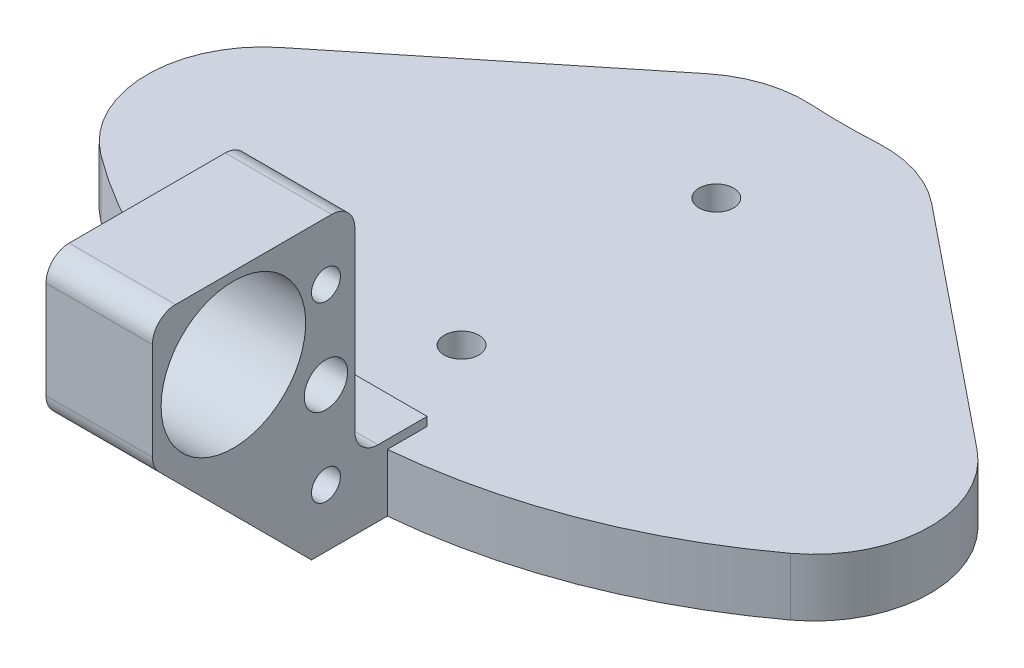
SolidWorks part; units mm, degrees
ref_plane "Front Plane" through (0, 0, 0) normal (0, 0, 1) x (1, 0, 0)
ref_plane "Top Plane" through (0, 0, 0) normal (0, 1, 0) x (1, 0, 0)
ref_plane "Right Plane" through (0, 0, 0) normal (1, 0, 0) x (0, 0, -1)
sketch "Sketch1" plane through (0, 0, 0) normal (0, 1, 0) x (1, 0, 0)
  line L0 (-49.3981, -39.9009) -> (-8.3458, -6.7413)
  line L1 (0, 0) -> (0, -63.5) construction
  line L2 (49.3981, -39.9009) -> (8.3458, -6.7413)
  arc A1 (-49.3981, -39.9009) -> (49.3981, -39.9009) centre (0, 0) ccw
  arc A2 (-8.3458, -6.7413) -> (8.3458, -6.7413) centre (0, 56.2079) ccw
  arc A3 (-56.9422, 28.1039) -> (-49.3981, -39.9009) centre (0, 0) ccw construction
  arc A4 (-56.9422, 28.1039) -> (-8.3458, -6.7413) centre (0, 56.2079) ccw construction
  arc A5 (8.3458, -6.7413) -> (56.9422, 28.1039) centre (0, 56.2079) ccw construction
  arc A6 (56.9422, 28.1039) -> (-56.9422, 28.1039) centre (0, 56.2079) ccw construction
  arc A7 (49.3981, -39.9009) -> (56.9422, 28.1039) centre (0, 0) ccw construction
  arc A8 (56.9422, 28.1039) -> (-56.9422, 28.1039) centre (0, 0) ccw construction
  dimension "D1" = 127
  dimension "D2" = 127
extrude "Boss-Extrude1" add sketch "Sketch1" along normal blind 6.35
sketch "Sketch3" plane through (0, 0, 0) normal (1, 0, 0) x (0, 0, -1)
  line L0 (0, 0) -> (-63.5, 0) construction
  line L1 (-58.8645, 0) -> (-71.5645, 0)
  line L2 (-73.152, 1.5875) -> (-73.152, 15.875) construction
  line L3 (-69.977, 0) -> (-69.977, 15.875) construction
  line L4 (-66.802, 9.8425) -> (-66.802, 15.875)
  line L5 (-64.262, 7.3025) -> (-58.8645, 7.3025)
  line L6 (-58.8645, 7.3025) -> (-58.8645, 0)
  line L7 (-66.802, 0) -> (-66.802, 7.3025) construction
  line L8 (-73.152, 15.875) -> (-73.152, 22.86) construction
  line L9 (-70.612, 31.75) -> (-69.342, 31.75)
  line L10 (-66.802, 29.21) -> (-66.802, 15.875)
  line L11 (-69.977, 31.75) -> (-69.977, 15.875) construction
  line L13 (-71.5645, 0) -> (-73.152, 1.5875)
  line L14 (-70.612, 31.75) -> (-86.487, 31.75)
  line L15 (-89.027, 29.21) -> (-89.027, 27.94)
  line L16 (-86.487, 25.4) -> (-75.692, 25.4) construction
  line L17 (-73.152, 25.4) -> (-73.152, 29.21) construction
  line L18 (-89.027, 28.575) -> (-73.152, 28.575) construction
  line L19 (-89.027, 27.94) -> (-89.027, 18.5146)
  line L20 (-88.2831, 16.7186) -> (-73.152, 1.5875)
  arc A0 (-73.152, 15.875) -> (-66.802, 15.875) centre (-69.977, 15.875) cw construction
  circle A1 centre (-69.977, 15.875) radius 2.3813
  circle A3 centre (-69.977, 25.4) radius 1.5875
  arc A4 (-73.152, 29.21) -> (-70.612, 31.75) centre (-70.612, 29.21) cw construction
  arc A5 (-69.342, 31.75) -> (-66.802, 29.21) centre (-69.342, 29.21) cw
  circle A6 centre (-69.977, 6.35) radius 1.5875
  arc A7 (-89.027, 27.94) -> (-86.487, 25.4) centre (-86.487, 27.94) ccw construction
  arc A8 (-86.487, 31.75) -> (-89.027, 29.21) centre (-86.487, 29.21) ccw
  circle A9 centre (-85.852, 28.575) radius 1.7145 construction
  arc A11 (-75.692, 25.4) -> (-73.152, 22.86) centre (-75.692, 22.86) cw construction
  arc A12 (-64.262, 7.3025) -> (-66.802, 9.8425) centre (-64.262, 9.8425) cw
  arc A13 (-89.027, 18.5146) -> (-88.2831, 16.7186) centre (-86.487, 18.5146) ccw
  circle A14 centre (-79.502, 28.575) radius 1.5875 construction
  point P4 (-73.152, 0)
  point P24 (0, 0)
  point P25 (-69.977, 6.35)
  point P26 (-69.977, 15.875)
  dimension "D3" = 3.175
  dimension "D6" = 2.54
  dimension "D7" = 4.7625
  dimension "D10" = 2.54
  dimension "D11" = 3.429
  dimension "D12" = 3.175
  dimension "D13" = 2.54
  dimension "D14" = 2.54
  dimension "D20" = 3.175
  dimension "D1" = 63.5
  dimension "D2" = 73.152
  dimension "D4" = 3.175
  dimension "D5" = 25.4
  dimension "D8" = 6.35
  dimension "D15" = 19.05
  dimension "D16" = 6.35
  dimension "D17" = 15.875
  dimension "D18" = 7.3025
  dimension "D19" = 12.7
  dimension "D21" = 12.7
  dimension "D22" = 22.225
extrude "Boss-Extrude2" add sketch "Sketch3" along normal blind 5.842 and the other way blind 5.842
fillet "Fillet1" radius 12.7 4 edges at (8.3458, 3.175, 6.7413) (-8.3458, 3.175, 6.7413) (-49.3981, 3.175, 39.9009) (49.3981, 3.175, 39.9009)
hole_wizard "Tap Drill for #10-24 Tap3" positions "Sketch4" profile "Sketch5" hole size "#10-24" standard "ANSI Inch" end condition through all
sketch "Sketch4" plane through (0, 0, 0) normal (0, -1, 0) x (-1, 0, 0)
  line L0 (5.842, -63.2307) -> (-5.842, -63.2307) construction
  line L1 (0, -63.2307) -> (0, -35.2614) construction
  line L2 (0, -35.2614) -> (0, -7.2921) construction
  arc A0 (-3.6526, -7.187) -> (3.6526, -7.187) centre (0, 56.2079) ccw construction
  point P17 (0, -21.2768)
  point P19 (0, -49.2461)
  point P25 (0, -21.2768)
sketch "Sketch5" plane through (0, 0, 49.2461) normal (1, 0, 0) x (0, 0, -1)
  line L0 (0, 0) -> (0, 31.75)
  line L1 (0, 31.75) -> (1.8986, 31.75)
  line L2 (1.8986, 31.75) -> (1.8986, 0)
  line L5 (1.8986, 0) -> (0, 0)
  line L11 (0, -6.35) -> (0, 107.95) construction
  dimension "Thru Hole Dia." = 3.7973
  dimension "Thru Hole Depth" = 31.75
sketch "Sketch6" plane through (-5.842, 0, 0) normal (-1, 0, 0) x (0, 0, 1)
  line L0 (80.137, 31.75) -> (80.137, 22.86) construction
  line L1 (69.342, 31.75) -> (86.487, 31.75) construction
  line L2 (89.027, 29.21) -> (89.027, 18.5146) construction
  circle A0 centre (80.137, 22.86) radius 7.9375
  point P4 (79.502, 22.8548)
  point P5 (79.502, 28.575)
  point P6 (79.5505, 31.75)
  point P11 (0, 0)
  dimension "D1" = 15.875
  dimension "D2" = 8.89
  dimension "D3" = 8.89
extrude "Cut-Extrude1" cut sketch "Sketch6" against normal through all
